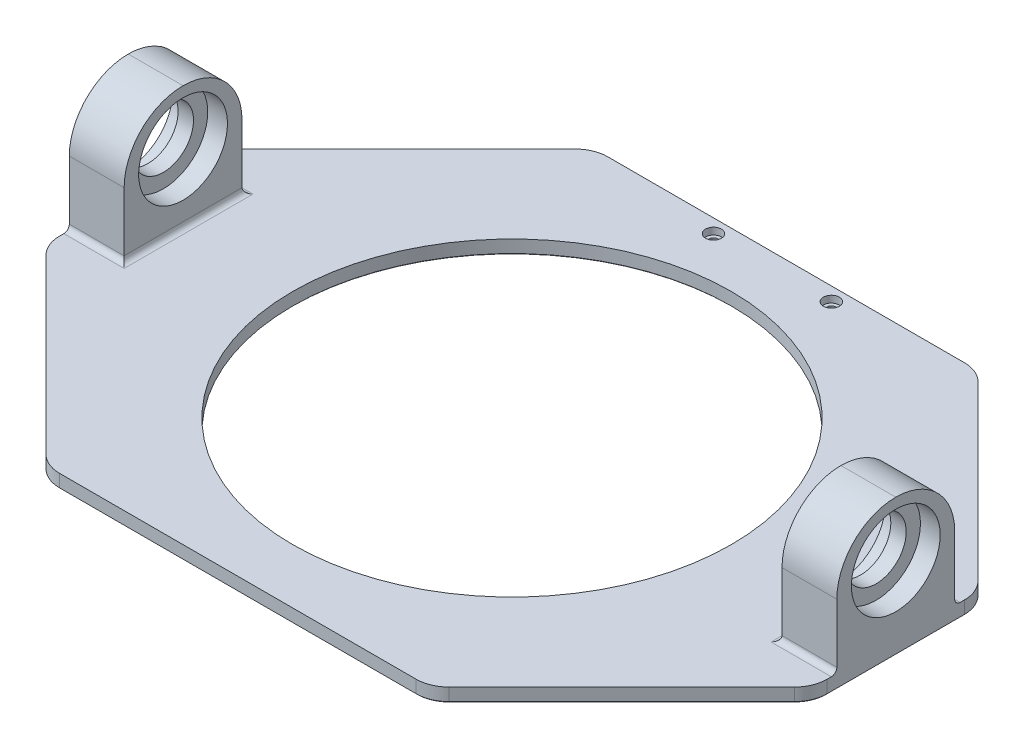
SolidWorks part; units mm, degrees
ref_plane "前视基准面" through (0, 0, 0) normal (0, 0, 1) x (1, 0, 0)
ref_plane "上视基准面" through (0, 0, 0) normal (0, 1, 0) x (1, 0, 0)
ref_plane "右视基准面" through (0, 0, 0) normal (1, 0, 0) x (0, 0, -1)
other "Configuration Table"
sketch "草图1" plane through (0, 0, 0) normal (0, 1, 0) x (1, 0, 0)
  line L1 (0, 0) -> (280, 0)
  line L2 (0, 0) -> (0, -280)
  line L3 (0, -280) -> (280, -280)
  line L4 (280, 0) -> (280, -280)
  dimension "D1" = 280
  dimension "D2" = 280
extrude "凸台-拉伸1" add sketch "草图1" along normal blind 5
sketch "草图2" plane through (0, 5, 0) normal (0, 1, 0) x (1, 0, 0)
  line L0 (0, -280) -> (280, -280) construction
  circle A0 centre (140, -180) radius 80
  point P4 (140, -280)
  dimension "D1" = 160
  dimension "D2" = 0
  dimension "D3" = 100
extrude "切除-拉伸1" cut sketch "草图2" against normal blind 5
sketch "草图3" plane through (0, 5, 0) normal (0, 1, 0) x (1, 0, 0)
  line L0 (0, 0) -> (0, -280) construction
  line L1 (0, -158.5) -> (20, -158.5)
  line L2 (0, -158.5) -> (0, -201.5)
  line L3 (0, -201.5) -> (20, -201.5)
  line L4 (20, -158.5) -> (20, -201.5)
  line L5 (280, -280) -> (280, 0) construction
  line L6 (280, -158.5) -> (260, -158.5)
  line L7 (280, -158.5) -> (280, -201.5)
  line L8 (280, -201.5) -> (260, -201.5)
  line L9 (260, -158.5) -> (260, -201.5)
  circle A0 centre (140, -180) radius 80 construction
  point P12 (20, -180)
  point P15 (260, -180)
  dimension "D1" = 0
  dimension "D2" = 0
  dimension "D3" = 43
  dimension "D4" = 43
  dimension "D5" = 20
  dimension "D6" = 20
extrude "凸台-拉伸2" add sketch "草图3" along normal blind 45
sketch "草图4" plane through (280, 0, 0) normal (1, 0, 0) x (0, 0, -1)
  line L0 (-201.5, 50) -> (-158.5, 50) construction
  circle A0 centre (-180, 30) radius 11
  point P4 (-180, 50)
  dimension "D1" = 0
  dimension "12.5" = 22
  dimension "D2" = 20
extrude "切除-拉伸2" cut sketch "草图4" against normal through all
sketch "草图5" plane through (280, 0, 0) normal (1, 0, 0) x (0, 0, -1)
  circle A0 centre (-180, 30) radius 16.2
  dimension "D1" = 32.4
extrude "切除-拉伸3" cut sketch "草图5" against normal blind 7.2
sketch "草图6" plane through (260, 0, 0) normal (-1, 0, 0) x (0, 0, 1)
  circle A0 centre (180, 30) radius 16.2
  dimension "D1" = 32.4
extrude "切除-拉伸4" cut sketch "草图6" against normal blind 7.2
sketch "草图7" plane through (20, 0, 0) normal (1, 0, 0) x (0, 0, -1)
  circle A0 centre (-180, 30) radius 16.2
  dimension "D1" = 32.4
extrude "切除-拉伸5" cut sketch "草图7" against normal blind 7.2
sketch "草图8" plane through (0, 0, 0) normal (-1, 0, 0) x (0, 0, 1)
  circle A0 centre (180, 30) radius 16.2
  dimension "D1" = 32.4
extrude "切除-拉伸6" cut sketch "草图8" against normal blind 7.2
sketch "草图9" plane through (0, 5, 0) normal (0, 1, 0) x (1, 0, 0)
  line L0 (280, -158.5) -> (280, 0) construction
  line L1 (0, 0) -> (280, 0)
  line L2 (0, 0) -> (0, -80)
  line L3 (0, -80) -> (280, -80)
  line L4 (280, 0) -> (280, -80)
  circle A0 centre (140, -180) radius 80 construction
  dimension "D1" = 100
extrude "切除-拉伸7" cut sketch "草图9" against normal through all
chamfer "倒角1" distance 70 angle 45 4 edges at (280, 2.5, 80) (280, 2.5, 280) (0, 2.5, 280) (0, 2.5, 80)
fillet "圆角1" radius 21.5 4 edges at (270, 50, 201.5) (270, 50, 158.5) (10, 50, 201.5) (10, 50, 158.5)
fillet "圆角2" radius 12 8 edges at (70, 2.5, 80) (210, 2.5, 80) (280, 2.5, 150) (280, 2.5, 210) (210, 2.5, 280) (70, 2.5, 280) (0, 2.5, 210) (0, 2.5, 150)
fillet "圆角3" radius 2 6 edges at (260, 5, 180) (270, 5, 201.5) (270, 5, 158.5) (10, 5, 158.5) (20, 5, 180) (10, 5, 201.5)
sketch "草图10" plane through (0, 0, 0) normal (0, -1, 0) x (-1, 0, 0)
  line L1 (-140, -80) -> (-140, -118.5005) construction
  line L3 (0, -154.9706) -> (0, -205.0294) construction
  line L4 (-74.9706, -80) -> (-205.0294, -80) construction
  circle A0 centre (-20, -187.5) radius 1.6
  circle A1 centre (-20, -172.5) radius 1.6
  circle A5 centre (-260, -187.5) radius 1.6
  circle A6 centre (-260, -172.5) radius 1.6
  circle A7 centre (-140, -180) radius 80 construction
  dimension "D1" = 3.2
  dimension "D2" = 3.2
  dimension "D4" = 20
  dimension "D5" = 15
  dimension "D6" = 7.5
  dimension "D3" = 20
extrude "切除-拉伸8" cut sketch "草图10" against normal blind 5
sketch "草图11" plane through (0, 0, 0) normal (0, -1, 0) x (-1, 0, 0)
  circle A4 centre (-20, -172.5) radius 2.35
  circle A5 centre (-20, -187.5) radius 2.35
  circle A6 centre (-260, -172.5) radius 2.35
  circle A7 centre (-260, -187.5) radius 2.35
  dimension "D1" = 4.7
  dimension "D2" = 4.7
  dimension "D3" = 4.7
  dimension "D4" = 4.7
extrude "切除-拉伸9" cut sketch "草图11" against normal blind 4.2
chamfer "倒角4" distance 0.4 angle 45 21 edges at (0.9134, 0, 150.3784) (0, 0, 180) (0.9134, 0, 209.6216) (35, 0, 245) (70.3784, 0, 279.0866) (140, 0, 280) (209.6216, 0, 279.0866) (245, 0, 245) (279.0866, 0, 209.6216) (280, 0, 180) (279.0866, 0, 150.3784) (245, 0, 115) (209.6216, 0, 80.9134) (140, 0, 80) (70.3784, 0, 80.9134) (35, 0, 115) (140, 0, 260) (20, 0, 170.15) (260, 0, 185.15) (260, 0, 170.15) (20, 0, 185.15)
sketch "草图12" plane through (0, 5, 0) normal (0, 1, 0) x (1, 0, 0)
  circle A0 centre (118.5, -85) radius 1.65
  circle A1 centre (161.5, -85) radius 1.65
  circle A3 centre (140, -180) radius 80 construction
  dimension "D1" = 43
  dimension "D2" = 21.5
  dimension "D3" = 95
  dimension "D4" = 95
  dimension "D5" = 3.3
  dimension "D6" = 3.3
extrude "切除-拉伸10" cut sketch "草图12" against normal blind 10
sketch "草图13" plane through (0, 5, 0) normal (0, 1, 0) x (1, 0, 0)
  circle A0 centre (118.5, -85) radius 2.9
  circle A1 centre (161.5, -85) radius 2.9
  dimension "D1" = 5.8
  dimension "D2" = 5.8
extrude "切除-拉伸11" cut sketch "草图13" against normal blind 2.5
